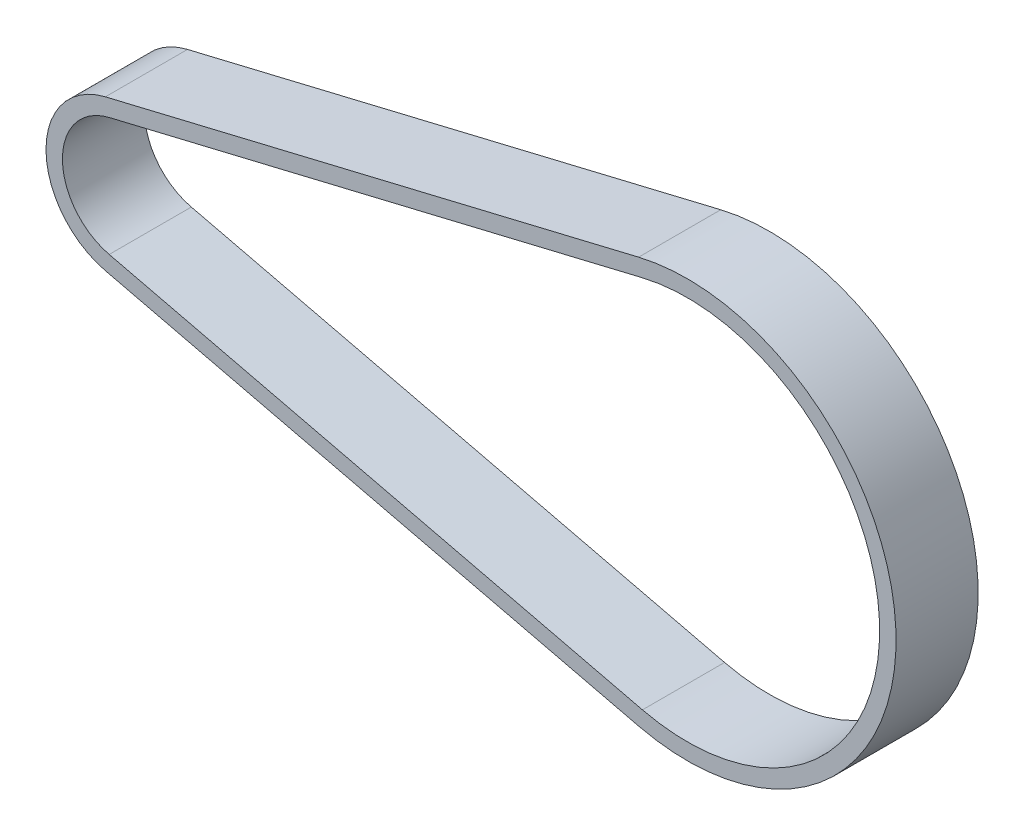
SolidWorks part; units mm, degrees
ref_plane "Front Plane" through (0, 0, 0) normal (0, 0, 1) x (1, 0, 0)
ref_plane "Top Plane" through (0, 0, 0) normal (0, 1, 0) x (1, 0, 0)
ref_plane "Right Plane" through (0, 0, 0) normal (1, 0, 0) x (0, 0, -1)
sketch "Sketch1" plane through (0, 0, 0) normal (0, 0, 1) x (1, 0, 0)
  line L0 (0, 0) -> (103, 0) construction
  line L1 (94.8118, 34.1736) -> (-2.5959, 10.8342)
  line L2 (94.8118, -34.1736) -> (-2.5959, -10.8342)
  line L3 (94.1128, 37.091) -> (-3.295, 13.7516)
  line L4 (94.1128, -37.091) -> (-3.295, -13.7516)
  circle A0 centre (0, 0) radius 11.1408 construction
  circle A1 centre (103, 0) radius 35.1408 construction
  arc A2 (-2.5959, -10.8342) -> (-2.5959, 10.8342) centre (0, 0) cw
  arc A3 (94.8118, 34.1736) -> (94.8118, -34.1736) centre (103, 0) cw
  arc A4 (-3.295, -13.7516) -> (-3.295, 13.7516) centre (0, 0) cw
  arc A5 (94.1128, 37.091) -> (94.1128, -37.091) centre (103, 0) cw
  circle A6 centre (0, 0) radius 9.5 construction
  circle A7 centre (103, 0) radius 33.5 construction
  dimension "D2" = 22.2817
  dimension "D6" = 19
  dimension "D8" = 67
  dimension "D3" = 70.2817
  dimension "D1" = 103
  dimension "D7" = 1.6408
  dimension "D4" = 3
extrude "Boss-Extrude1" add sketch "Sketch1" along normal blind 15
equation "\"D7@Sketch1\"=(\"D2@Sketch1\"-\"D6@Sketch1\")/2"
